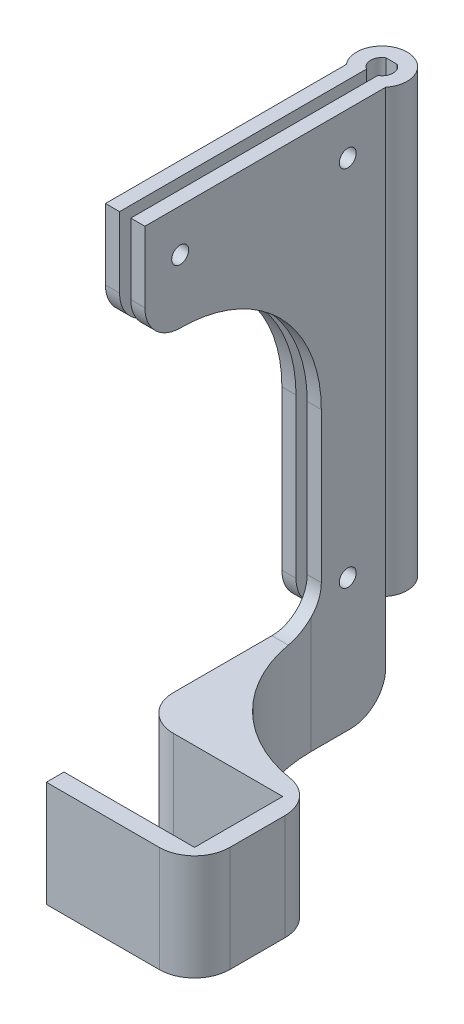
SolidWorks part; units mm, degrees
ref_plane "Front Plane" through (0, 0, 0) normal (0, 0, 1) x (1, 0, 0)
ref_plane "Top Plane" through (0, 0, 0) normal (0, 1, 0) x (1, 0, 0)
ref_plane "Right Plane" through (0, 0, 0) normal (1, 0, 0) x (0, 0, -1)
sketch "Sketch1" plane through (0, 0, 0) normal (0, 1, 0) x (1, 0, 0)
  line L0 (-1.5875, -2.7496) -> (-1.5875, -22.7496)
  line L1 (1.5875, -2.7496) -> (1.5875, -22.7496)
  line L2 (1.5875, 2.7496) -> (-1.5875, 2.7496)
  line L3 (5.5875, -4.5012) -> (5.5875, -22.7496)
  line L4 (-5.5875, -4.5012) -> (-5.5875, -22.7496)
  line L5 (-5.5875, -22.7496) -> (-1.5875, -22.7496)
  line L6 (1.5875, -22.7496) -> (5.5875, -22.7496)
  arc A0 (1.5875, -2.7496) -> (1.5875, 2.7496) centre (0, 0) ccw
  arc A1 (5.5875, -4.5012) -> (-5.5875, -4.5012) centre (0, 0) ccw
  arc A2 (-1.5875, 2.7496) -> (-1.5875, -2.7496) centre (0, 0) ccw
  arc A4 (1.5875, -2.7496) -> (-1.5875, -2.7496) centre (0, 0) ccw construction
  dimension "D1" = 3.175
  dimension "D2" = 20
  dimension "D3" = 3.175
  dimension "D5" = 3.175
  dimension "D4" = 4
extrude "Boss-Extrude1" add sketch "Sketch1" along normal blind 125
sketch "Sketch5" plane through (0, 125, 0) normal (0, 1, 0) x (1, 0, 0)
  line L1 (-1.5875, -110.675) -> (-1.5875, -105.675)
  line L2 (-47.5875, -105.675) -> (-47.5875, -140.675)
  line L3 (-47.5875, -140.675) -> (-1.5875, -140.675)
  line L4 (-1.5875, -140.675) -> (-1.5875, -135.675)
  line L5 (-1.5875, -135.675) -> (-42.5875, -135.675)
  line L9 (-1.5875, -22.7496) -> (-1.5875, -2.7496) construction
  line L10 (-42.5875, -110.675) -> (-1.5875, -110.675)
  line L12 (-42.5875, -135.675) -> (-42.5875, -110.675)
  line L13 (-47.5875, -105.675) -> (-1.5875, -105.675)
  line L18 (-18.6703, -3.175) -> (17.7565, -3.175) construction
  circle A0 centre (0, 0) radius 3.175 construction
  arc A1 (-1.5875, 2.7496) -> (-1.5875, -2.7496) centre (0, 0) ccw construction
  point P2 (-42.5875, -123.175)
  dimension "D2" = 120
  dimension "D1" = 41
  dimension "D3" = 25
  dimension "D4" = 5
  dimension "D5" = 5
  dimension "D7" = 5
extrude "Boss-Extrude2" [suppressed] add sketch "Sketch5" against normal mid plane 30 from offset 137.5 offset against normal yes
sketch "Sketch6" plane through (0, 125, 0) normal (0, 1, 0) x (1, 0, 0)
  line L0 (5.5875, -22.7496) -> (5.5875, -4.5012) construction
  line L1 (1.5875, -22.7496) -> (5.5875, -22.7496)
  line L2 (1.5875, -22.7496) -> (1.5875, -72.7496)
  line L3 (1.5875, -72.7496) -> (5.5875, -72.7496)
  line L4 (5.5875, -22.7496) -> (5.5875, -72.7496)
  line L6 (-1.5875, -22.7496) -> (-1.5875, -2.7496) construction
  line L7 (-5.5875, -22.7496) -> (-1.5875, -22.7496)
  line L8 (-5.5875, -22.7496) -> (-5.5875, -72.7496)
  line L9 (-5.5875, -72.7496) -> (-1.5875, -72.7496)
  line L10 (-1.5875, -22.7496) -> (-1.5875, -72.7496)
  dimension "D1" = 50
extrude "Boss-Extrude3" add sketch "Sketch6" against normal blind 30
hole_wizard "M4 Clearance Hole1" positions "Sketch2" profile "Sketch3" hole size "M4" standard "ANSI Metric" end condition through all
sketch "Sketch2" plane through (5.5875, 0, 0) normal (1, 0, 0) x (0, 0, -1)
  line L4 (-72.7496, 125) -> (-4.5012, 125) construction
  line L6 (-72.7496, 95) -> (-72.7496, 125) construction
  point P0 (-15.2496, 113)
  point P4 (-15.2496, 10)
  point P19 (-62.7496, 113)
  dimension "D1" = 103
  dimension "D2" = 12
  dimension "D3" = 47.5
  dimension "D4" = 10
sketch "Sketch3" plane through (5.5875, 113, 15.2496) normal (0, 1, 0) x (0, 0, -1)
  line L0 (0, 0) -> (0, 12.7625)
  line L1 (0, 12.7625) -> (2.4, 12.7625)
  line L2 (2.4, 12.7625) -> (2.4, 0)
  line L5 (2.4, 0) -> (0, 0)
  line L11 (0, -6.35) -> (0, 107.95) construction
  dimension "Thru Hole Dia." = 4.8
  dimension "Thru Hole Depth" = 12.7625
sketch "Sketch9" [suppressed] plane through (-1.5875, 0, 0) normal (1, 0, 0) x (0, 0, -1)
  line L0 (-105.675, 2.5) -> (-22.7496, 2.5)
  line L1 (-105.675, 2.5) -> (-105.675, -27.5)
  line L2 (-105.675, -27.5) -> (-22.7496, -27.5)
  line L3 (-22.7496, 95) -> (-22.7496, 0) construction
  line L5 (-4.5012, 0) -> (-4.5012, -27.5)
  line L6 (-4.5012, -27.5) -> (-22.7496, -27.5)
  line L7 (-22.7496, 2.5) -> (-22.7496, 0)
  line L8 (-22.7496, 95) -> (-22.7496, 0) construction
  line L9 (-22.7496, 0) -> (-4.5012, 0) construction
  line L10 (-22.7496, 0) -> (-4.5012, 0)
extrude "Boss-Extrude5" [suppressed] add sketch "Sketch9" against normal up to surface (4 mm away) up to face at (-5.5875, 113, 12.8496)
chamfer "Chamfer2" [suppressed] distance 42 distance2 35
fillet "Fillet1" [suppressed] radius 40
fillet "Fillet2" [suppressed] radius 10
ref_plane "Plane1" through (0, 0, 0) normal (-1, 0, 0) x (0, 0, 1)
ref_plane "Plane2" through (0, -15, 0) normal (0, 1, 0) x (1, 0, 0)
ref_axis "Axis1" through (0, -15, 76.2496) along (0, 0, -1)
sketch "Sketch11" plane through (0, 125, 0) normal (0, 1, 0) x (1, 0, 0)
  line L0 (-21.2191, -3.175) -> (29.064, -3.175) construction
  line L1 (5.5875, -65.675) -> (47.5875, -65.675)
  line L2 (5.5875, -72.7496) -> (5.5875, -4.5012) construction
  line L3 (47.5875, -65.675) -> (47.5875, -100.675)
  line L4 (47.5875, -100.675) -> (5.5875, -100.675)
  line L5 (5.5875, -100.675) -> (5.5875, -95.675)
  line L6 (5.5875, -95.675) -> (42.5875, -95.675)
  line L7 (42.5875, -95.675) -> (42.5875, -70.675)
  line L8 (42.5875, -70.675) -> (5.5875, -70.675)
  line L9 (5.5875, -70.675) -> (5.5875, -65.675)
  line L10 (1.5875, -2.7496) -> (1.5875, -72.7496) construction
  circle A0 centre (0, 0) radius 3.175 construction
  arc A1 (-1.5875, 2.7496) -> (-1.5875, -2.7496) centre (0, 0) ccw construction
  point P17 (42.5875, -83.175)
  dimension "D1" = 5
  dimension "D2" = 5
  dimension "D3" = 5
  dimension "D4" = 41
  dimension "D5" = 80
  dimension "D6" = 25
extrude "Boss-Extrude6" add sketch "Sketch11" along normal mid plane 30 from offset 137.5 offset against normal yes
sketch "Sketch13" plane through (5.5875, 0, 0) normal (-1, 0, 0) x (0, 0, 1)
  line L0 (70.675, 2.5) -> (22.7496, 2.5)
  line L1 (22.7496, 95) -> (22.7496, 0) construction
  line L2 (22.7496, 2.5) -> (22.7496, 0)
  line L3 (22.7496, 0) -> (4.5012, 0)
  line L4 (70.675, 2.5) -> (70.675, -27.5)
  line L5 (70.675, -27.5) -> (4.5012, -27.5)
  line L6 (4.5012, -27.5) -> (4.5012, 0)
extrude "Boss-Extrude8" add sketch "Sketch13" along normal up to surface (4 mm away) up to face at (1.5875, 113, 12.8496)
chamfer "Chamfer3" [suppressed] distance 42 distance2 35
fillet "Fillet5" radius 40 3 edges at (3.5875, 95, 22.7496) (-3.5875, 95, 22.7496) (5.5875, -12.5, 65.675)
fillet "Fillet4" radius 10 8 edges at (3.5875, -27.5, 4.5012) (1.5875, -12.5, 70.675) (3.5875, 2.5, 22.7496) (47.5875, -12.5, 100.675) (-3.5875, 95, 72.7496) (3.5875, 95, 72.7496) (47.5875, -12.5, 65.675) (-3.5875, 0, 22.7496)
sketch "Sketch14" [suppressed] plane through (0, 0, 110.675) normal (0, 0, 1) x (1, 0, 0)
  line L5 (-47.5875, -27.5) -> (-47.5875, 2.5) construction
  line L6 (-40.0875, -7.5) -> (-40.0875, -17.5) construction
  line L7 (-37.5875, -7.5) -> (-37.5875, -17.5)
  line L8 (-42.5875, -7.5) -> (-42.5875, -17.5)
  line L9 (-42.5875, -27.5) -> (-42.5875, 2.5) construction
  arc A0 (-37.5875, -7.5) -> (-42.5875, -7.5) centre (-40.0875, -7.5) ccw
  arc A1 (-42.5875, -17.5) -> (-37.5875, -17.5) centre (-40.0875, -17.5) ccw
  point P2 (-40.0875, -12.5)
  point P9 (-47.5875, -12.5)
  dimension "D1" = 5
  dimension "D2" = 10
extrude "Cut-Extrude1" [suppressed] cut sketch "Sketch14" against normal up to next
sketch "Sketch15" plane through (0, 0, 70.675) normal (0, 0, 1) x (1, 0, 0)
  line L0 (40.0875, -7.5) -> (40.0875, -17.5) construction
  line L1 (42.5875, -7.5) -> (42.5875, -17.5)
  line L2 (37.5875, -7.5) -> (37.5875, -17.5)
  line L3 (42.5875, 2.5) -> (42.5875, -27.5) construction
  arc A0 (42.5875, -7.5) -> (37.5875, -7.5) centre (40.0875, -7.5) ccw
  arc A1 (37.5875, -17.5) -> (42.5875, -17.5) centre (40.0875, -17.5) ccw
  point P2 (40.0875, -12.5)
  point P9 (42.5875, -12.5)
  dimension "D1" = 5
  dimension "D2" = 10
extrude "Cut-Extrude2" cut sketch "Sketch15" against normal up to next
